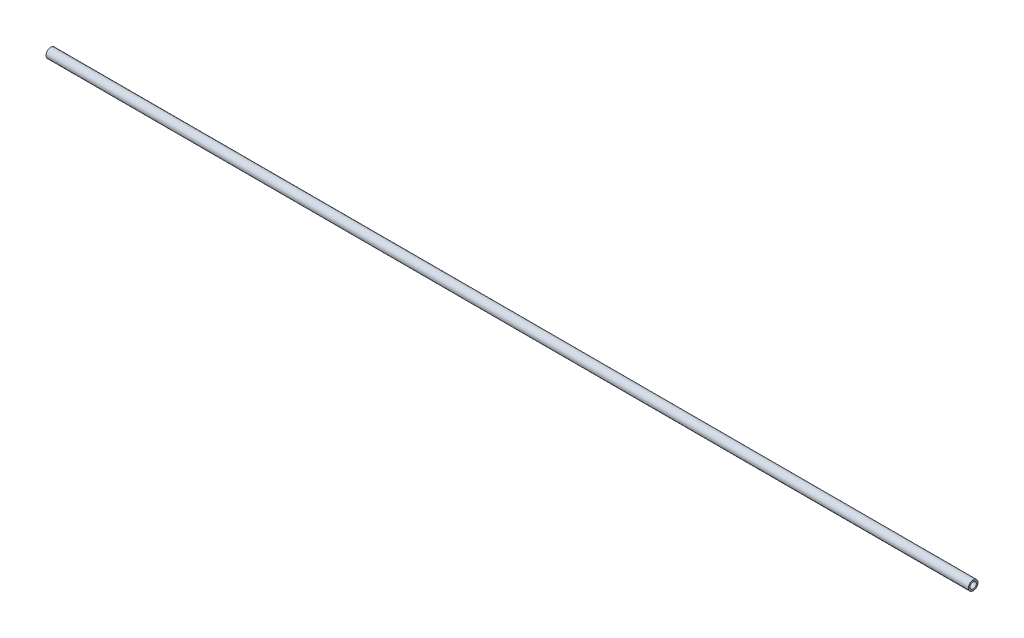
SolidWorks part; units mm, degrees
ref_plane "Front Plane" through (0, 0, 0) normal (0, 0, 1) x (1, 0, 0)
ref_plane "Top Plane" through (0, 0, 0) normal (0, 1, 0) x (1, 0, 0)
ref_plane "Right Plane" through (0, 0, 0) normal (1, 0, 0) x (0, 0, -1)
sketch "Sketch1" plane through (0, 0, 0) normal (1, 0, 0) x (0, 0, -1)
  circle A0 centre (0, 0) radius 3
  circle A1 centre (0, 0) radius 2
  dimension "D1" = 6
  dimension "D2" = 4
extrude "Boss-Extrude1" add sketch "Sketch1" along normal blind 290 and the other way blind 290
